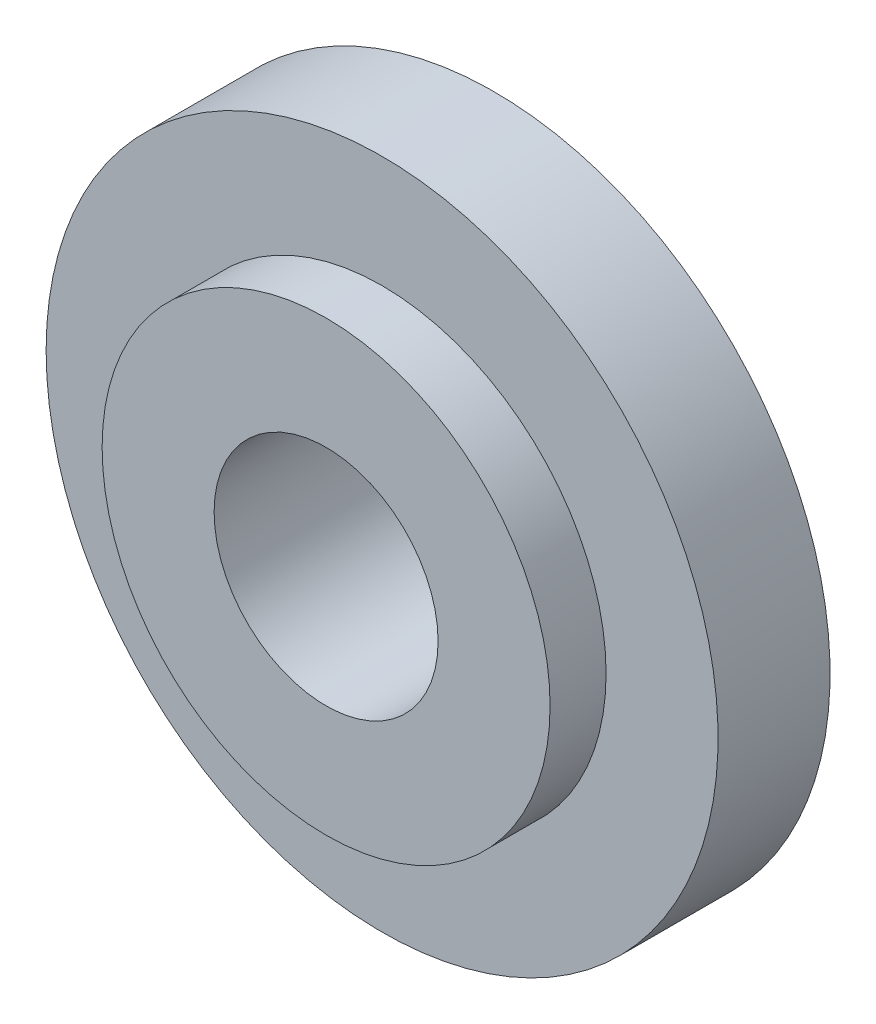
SolidWorks part; units mm, degrees
material "Сталь ШХ15 ГОСТ 801-78"
ref_plane "Plane1" through (0, 0, 0) normal (0, 0, 1) x (1, 0, 0)
ref_plane "Plane2" through (0, 0, 0) normal (0, 1, 0) x (1, 0, 0)
ref_plane "Plane3" through (0, 0, 0) normal (1, 0, 0) x (0, 0, -1)
sketch "Эскиз1" plane through (0, 0, 0) normal (0, 0, 1) x (1, 0, 0)
  circle A0 centre (0, 0) radius 4
  dimension "D1" = 8
extrude "Бобышка-Вытянуть1" add sketch "Эскиз1" along normal blind 3 contours A0
sketch "Эскиз3" plane through (0, 0, 0) normal (0, 0, -1) x (-1, 0, 0)
  circle A0 centre (0, 0) radius 6
  dimension "D1" = 12
extrude "Бобышка-Вытянуть2" add sketch "Эскиз3" against normal blind 2
sketch "Эскиз4" plane through (0, 0, 3) normal (0, 0, 1) x (1, 0, 0)
  circle A0 centre (0, 0) radius 2
  dimension "D1" = 4
extrude "Вырез-Вытянуть1" cut sketch "Эскиз4" against normal through all both and the other way through all
